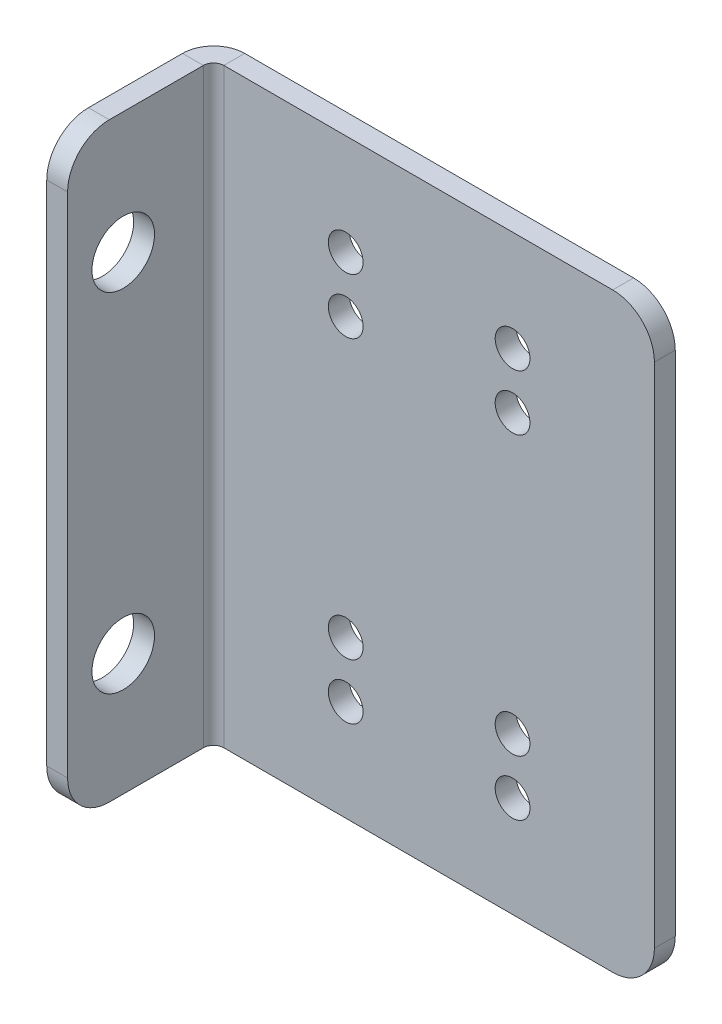
SolidWorks part; units mm, degrees
note: The reader was unsure of these and kept them because the rebuilt part matched: flange length of "边线-法兰1".
ref_plane "前视基准面" through (0, 0, 0) normal (0, 0, 1) x (1, 0, 0)
ref_plane "上视基准面" through (0, 0, 0) normal (0, 1, 0) x (1, 0, 0)
ref_plane "右视基准面" through (0, 0, 0) normal (1, 0, 0) x (0, 0, -1)
sketch "草图1" plane through (0, 0, 0) normal (0, 0, 1) x (1, 0, 0)
  line L1 (16.6, -21.25) -> (-16.6, -21.25)
  line L2 (16.6, -21.25) -> (16.6, 21.25)
  line L3 (16.6, 21.25) -> (-16.6, 21.25)
  line L4 (-16.6, -21.25) -> (-16.6, 21.25)
  line L5 (16.6, -21.25) -> (-16.6, 21.25) construction
  line L6 (16.6, 21.25) -> (-16.6, -21.25) construction
  point P0 (0, 0)
  dimension "D1" = 42.5
  dimension "D2" = 33.2
base flange "基体-法兰1" sketch "草图1" thickness 1.5 reverse thickness direction no parameters "D1"=0.7366
edge flange "边线-法兰1" sketch "草图8" flange angle 90 flange length 12 flange position material inside bend radius 0.7366 thickness 1.5 relief rectangular parameters "D6"=10
sketch "草图8" plane through (-16.6, 0, 0) normal (-1, 0, 0) x (0, -1, 0)
  line L2 (-21.25, 0) -> (-21.25, 10.5)
  line L3 (-21.25, 10.5) -> (21.25, 10.5)
  line L4 (21.25, 10.5) -> (21.25, 0)
  line L7 (-21.25, 0) -> (21.25, 0) construction
  line L8 (-21.25, 0) -> (21.25, 0)
bend "边线折弯1" bend radius 0.7366 bend angle 90 parameters "D5"=1
sketch "草图9" plane through (0, 0, 0) normal (0, 0, 1) x (1, 0, 0)
  circle A0 centre (6.4, 14) radius 1.25
  circle A1 centre (-5.6, 14) radius 1.25
  circle A2 centre (6.4, -10) radius 1.25
  circle A3 centre (-5.6, -10) radius 1.25
  dimension "D1" = 2.5
extrude "切除-拉伸1" cut sketch "草图9" against normal blind 10
sketch "草图10" plane through (-15.1, 0, 0) normal (1, 0, 0) x (0, 0, -1)
  line L0 (0, 0) -> (-10.5, 0) construction
  line L1 (-10.5, -21.25) -> (-10.5, 21.25) construction
  circle A0 centre (-6.5, 12.5) radius 2.25
  circle A1 centre (-6.5, -12.5) radius 2.25
  dimension "D2" = 4
  dimension "D3" = 4.5
  dimension "D1" = 25
extrude "切除-拉伸2" cut sketch "草图10" against normal blind 10
mirror "镜向1" about plane through (0, 0, 0) normal (0, 1, 0) of "切除-拉伸1"
fillet "圆角1" radius 3 4 edges at (-15.85, -21.25, 10.5) (16.6, -21.25, -0.75) (16.6, 21.25, -0.75) (-15.85, 21.25, 10.5)
sketch "折弯-线1" plane through (0, 0, 0) normal (0, 1, 0) x (1, 0, 0)
sketch "边界框1" plane through (0, 0, 0) normal (0, 1, 0) x (1, 0, 0)
sheet metal parameters "钣金6" thickness 1.5 parameters "D1"=0.7366
flat pattern "平板型式6" [suppressed]
sketch "折弯-线2" plane through (0, 0, 0) normal (0, 1, 0) x (1, 0, 0)
sketch "边界框2" [suppressed] plane through (0, 0, 0) normal (0, 1, 0) x (1, 0, 0)
sheet metal parameters "钣金7" thickness 1.5 parameters "D1"=0.7366
flat pattern "平板型式6" [suppressed]
sketch "折弯-线2" plane through (0, 0, 0) normal (0, 1, 0) x (1, 0, 0)
sketch "边界框2" [suppressed] plane through (0, 0, 0) normal (0, 1, 0) x (1, 0, 0)
bend of the flat pattern "展平-<边线折弯1>1"
sheet metal parameters "钣金8" thickness 1.5 parameters "D1"=0.7366
flat pattern "平板型式6" [suppressed]
sketch "折弯-线2" plane through (0, 0, 0) normal (0, 1, 0) x (1, 0, 0)
sketch "边界框2" [suppressed] plane through (0, 0, 0) normal (0, 1, 0) x (1, 0, 0)
bend of the flat pattern "展平-<边线折弯1>1"
sheet metal parameters "钣金9" thickness 1.5 parameters "D1"=0.7366
flat pattern "平板型式6" [suppressed]
sketch "折弯-线2" plane through (0, 0, 0) normal (0, 1, 0) x (1, 0, 0)
sketch "边界框2" [suppressed] plane through (0, 0, 0) normal (0, 1, 0) x (1, 0, 0)
bend of the flat pattern "展平-<边线折弯1>1"
sheet metal parameters "钣金10" thickness 1.5 parameters "D1"=0.7366
flat pattern "平板型式6" [suppressed]
sketch "折弯-线2" plane through (0, 0, 0) normal (0, 1, 0) x (1, 0, 0)
sketch "边界框2" [suppressed] plane through (0, 0, 0) normal (0, 1, 0) x (1, 0, 0)
bend of the flat pattern "展平-<边线折弯1>1"
